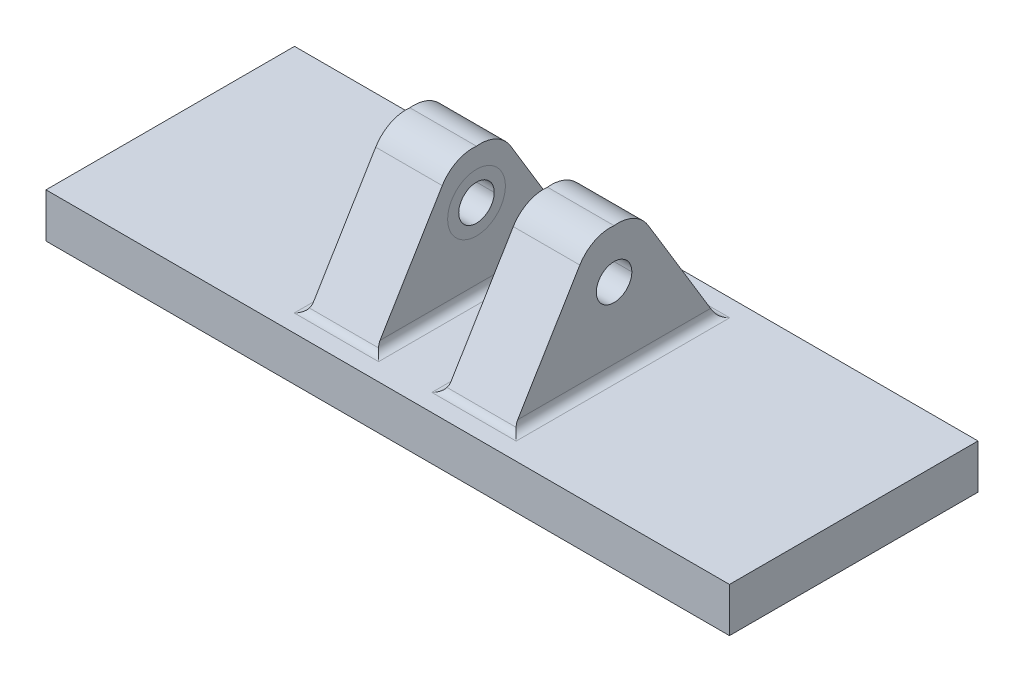
SolidWorks part; units mm, degrees
material "Onyx"
ref_plane "Front Plane" through (0, 0, 0) normal (0, 0, 1) x (1, 0, 0)
ref_plane "Top Plane" through (0, 0, 0) normal (0, 1, 0) x (1, 0, 0)
ref_plane "Right Plane" through (0, 0, 0) normal (1, 0, 0) x (0, 0, -1)
sketch "Sketch1" plane through (0, 0, 0) normal (0, 1, 0) x (1, 0, 0)
  line L1 (77, 28) -> (-77, 28)
  line L2 (77, 28) -> (77, -28)
  line L3 (77, -28) -> (-77, -28)
  line L4 (-77, 28) -> (-77, -28)
  line L5 (77, 28) -> (-77, -28) construction
  line L6 (77, -28) -> (-77, 28) construction
  point P0 (0, 0)
  dimension "D1" = 154
  dimension "D2" = 56
extrude "Boss-Extrude1" add sketch "Sketch1" along normal blind 10
sketch "Sketch2" plane through (0, 0, 0) normal (1, 0, 0) x (0, 0, -1)
  line L1 (-22.9345, 10) -> (-7.7143, 35.1803)
  line L3 (0, 0) -> (0, 39.0224) construction
  line L4 (-22.9345, 10) -> (22.9345, 10)
  line L5 (22.9345, 10) -> (7.7143, 35.1803)
  line L6 (-28, 0) -> (28, 0) construction
  line L8 (28, 10) -> (-28, 10) construction
  circle A0 centre (0, 28) radius 4
  arc A1 (-7.7143, 35.1803) -> (0, 39.0224) centre (-0.827, 31.0173) cw
  arc A2 (7.7143, 35.1803) -> (0, 39.0224) centre (0.827, 31.0173) ccw
  point P14 (0, 10)
  dimension "D2" = 8
  dimension "D1" = 28
extrude "Boss-Extrude2" add sketch "Sketch2" along normal blind 15 from offset 8
mirror "Mirror1" about plane through (0, 0, 0) normal (1, 0, 0) of "Boss-Extrude2"
ref_plane "Plane1" through (0, 28, 0) normal (0, -1, 0) x (-1, 0, 0)
split line "Split Line1"
sketch "Sketch3" plane through (-8, 0, 0) normal (1, 0, 0) x (0, 0, -1)
  circle A0 centre (0, 28) radius 6.5
  dimension "D1" = 13
split line "Split Line2"
sketch "Sketch4" plane through (8, 0, 0) normal (-1, 0, 0) x (0, 0, 1)
  circle A0 centre (0, 28) radius 6.5
  dimension "D1" = 13
split line "Split Line3"
fillet "Fillet1" radius 2 8 edges at (15.5, 10, 22.9345) (23, 10, 0) (8, 10, 0) (15.5, 10, -22.9345) (-15.5, 10, -22.9345) (-23, 10, 0) (-15.5, 10, 22.9345) (-8, 10, 0)
chamfer "Chamfer1" [suppressed] distance 10 angle 45
fillet "Fillet2" [suppressed] radius 2
